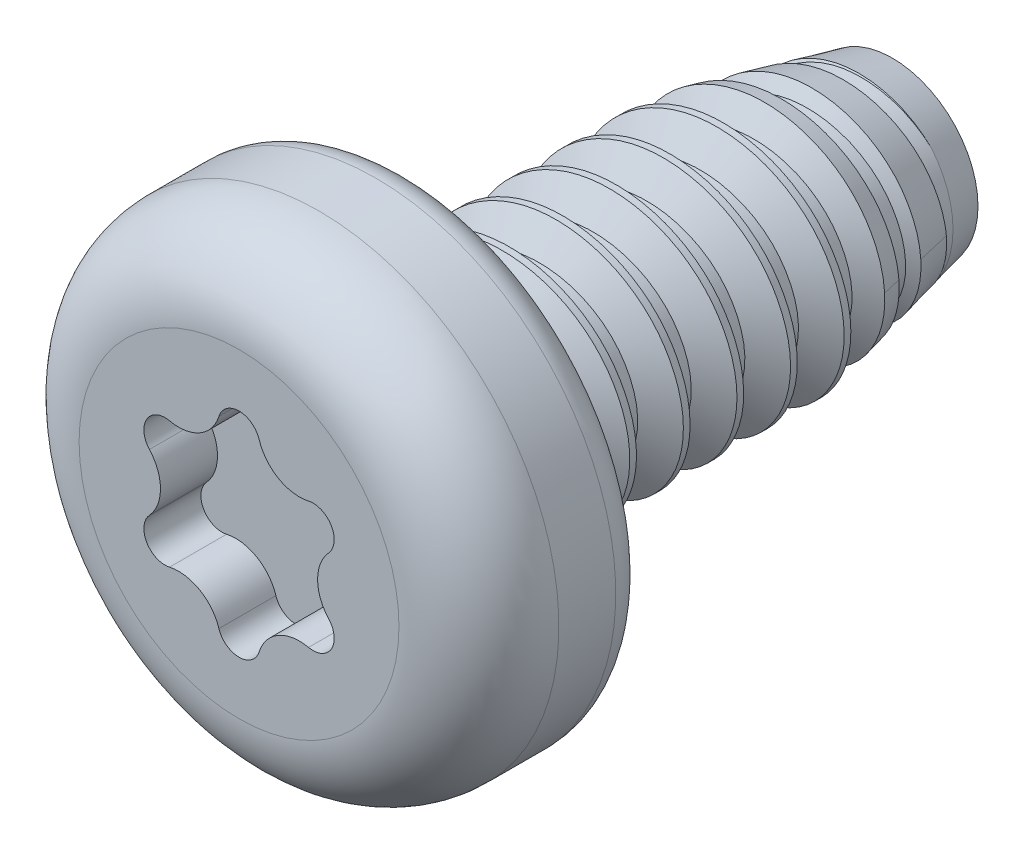
SolidWorks part; units mm, degrees
note: '?' marks a value the reader was unsure of.
ref_plane "Front" through (0, 0, 0) normal (0, 0, 1) x (1, 0, 0)
ref_plane "Top" through (0, 0, 0) normal (0, 1, 0) x (1, 0, 0)
ref_plane "Right" through (0, 0, 0) normal (1, 0, 0) x (0, 0, -1)
sketch "Sketch1" plane through (0, 0, 0) normal (0, 0, 1) x (1, 0, 0)
  circle A0 centre (0, 0) radius 4.7371
  dimension "Head Dia" = 9.4742
extrude "Extrude3" add sketch "Sketch1" along normal blind 3.3782
ref_plane "Plane1" through (0, 0, 3.3782) normal (0, 0, 1) x (1, 0, 0)
sketch "Sketch11" plane through (0, 0, 0) normal (1, 0, 0) x (0, 0, -1)
  line L2 (-3.3782, 4.7371) -> (-3.3782, -4.7371) construction
  line L4 (0, 4.7371) -> (-3.3782, 4.7371) construction
  line L5 (-1.7992, 4.7371) -> (-0.6756, 4.7371)
  line L6 (0, -4.7371) -> (0, 4.7371) construction
  line L7 (-3.3782, 4.7371) -> (-3.3782, 3.1581) construction
  line L8 (-3.3782, 1.579) -> (-3.3782, 0) construction
  line L9 (-3.3782, 3.1581) -> (-3.3782, 1.579) construction
  line L10 (-3.3782, 3.1581) -> (-3.6322, 3.1581)
  line L11 (0, 0) -> (-3.3782, 0) construction
  line L12 (-3.6322, 3.1581) -> (-3.6322, 4.9911)
  line L13 (-3.6322, 4.9911) -> (0.254, 4.9911)
  line L14 (0.254, 4.9911) -> (0.254, 4.0615)
  line L15 (0.254, 4.0615) -> (0, 4.0615)
  arc A0 (-3.3782, 3.1581) -> (-1.7992, 4.7371) centre (-1.7992, 3.1581) cw
  arc A1 (-0.6756, 4.7371) -> (0, 4.0615) centre (-0.6756, 4.0615) cw
  dimension "D1" = 0.6756
  dimension "D2" = 0.254
  dimension "D3" = 0.254
revolve "Cut-Revolve3" cut sketch "Sketch11" angle 360 about L11
sketch "Sketch14" plane through (0, 0, 0) normal (1, 0, 0) x (0, 0, -1)
  line L0 (0.2646, 1.8402) -> (0.5953, 2.413) construction
  line L2 (0.5953, 2.413) -> (0.7276, 2.413)
  line L3 (0.7276, 2.413) -> (1.0583, 1.8402) construction
  line L4 (1.0583, 1.8402) -> (0.2646, 1.8402) construction
  line L5 (1.0583, 1.8402) -> (1.3229, 1.8402) construction
  line L6 (0.2646, 1.8402) -> (0, 1.8402) construction
  line L10 (0, 4.7371) -> (0, -4.7371) construction
  line L11 (0.5953, 2.413) -> (0.2646, 1.8402)
  line L12 (0.2646, 1.8402) -> (1.0583, 1.8402)
  line L13 (1.0583, 1.8402) -> (0.7276, 2.413)
  line L14 (0, 0) -> (-3.3782, 0) construction
  line L15 (0, 0) -> (-3.3782, 0) construction
  point P11 (0.6615, 2.413)
  dimension "D1" = 60
  dimension "Pitch" = 1.0583
  dimension "D3" = 0.2646
  dimension "D4" = 0.1323
  dimension "Screw Dia" = 4.826
ref_plane "Plane2" through (0, 0, -0.6615) normal (0, 0, 1) x (1, 0, 0)
sketch "Sketch15" plane through (0, 0, -0.6615) normal (0, 0, 1) x (1, 0, 0)
  circle A0 centre (0, 0) radius 2.413
curve "Helix/Spiral1" pitch 1.0583 height 1.5875 radius 2.413 centre (0, 0, -0.6615) axis (0, 0, -1) start towards (0, 1, 0)
sketch "Sketch17" plane through (0, 0, 0) normal (1, 0, 0) x (0, 0, -1)
  line L1 (0, 0) -> (9.525, 0)
  line L2 (0, 0) -> (0, 1.8402)
  line L3 (0, 1.8402) -> (9.525, 1.8402)
  line L4 (9.525, 0) -> (9.525, 1.8402)
  dimension "Body Length" = 9.525
revolve "Revolve1" add sketch "Sketch17" angle 360 about L11
sweep "Sweep1" add profiles "Sketch14" path "Helix/Spiral1"
pattern_linear "LPattern3" count 8 spacing 1.0583 along (0, 0, -1) count 2 spacing 1.0583 along (0, 0, 1) of "Sweep1"
sketch "Sketch13" plane through (0, 0, 0) normal (1, 0, 0) x (0, 0, -1)
  line L0 (9.525, 1.6891) -> (6.4364, 2.413)
  line L1 (9.525, 1.6891) -> (9.525, -1.6891) construction
  line L2 (6.4364, 2.413) -> (9.525, 2.413)
  line L3 (9.525, 2.413) -> (9.525, 1.6891) construction
  line L4 (9.525, 1.6891) -> (9.525, 0)
  line L5 (0, 0) -> (9.525, 0) construction
  line L6 (0.5953, 2.413) -> (0.7276, 2.413) construction
  line L7 (12.065, 0) -> (12.065, 2.413)
  line L8 (12.065, 2.413) -> (9.525, 2.413)
  line L9 (9.525, 0) -> (12.065, 0)
  dimension "D3" = 2.54
  dimension "D1" = 13.191
  dimension "D2" = 3.3782
revolve "Cut-Revolve4" cut sketch "Sketch13" angle 360 about L5
sketch "Sketch12" plane through (0, 0, 3.3782) normal (0, 0, 1) x (1, 0, 0)
  line L0 (0, 0) -> (0, 2.1054) construction
  line L1 (0, 0) -> (0.7756, 1.3434) construction
  line L2 (0, 0) -> (-0.7756, 1.3434) construction
  line L3 (-0.7756, 1.3434) -> (0, 0)
  line L4 (0, 0) -> (0.7756, 1.3434)
  arc A0 (-0.7756, 1.3434) -> (-0.3975, 1.8141) centre (-1.1925, 2.0654) ccw
  arc A1 (-0.3975, 1.8141) -> (0.3975, 1.8141) centre (0, 1.6885) cw
  arc A2 (0.3975, 1.8141) -> (0.7756, 1.3434) centre (1.1925, 2.0654) ccw
  circle A5 centre (0, 0) radius 2.1054 construction
  dimension "M" = 4.2108
  dimension "D2" = 0.4169
  dimension "D3" = 0.8337
  dimension "D1" = 60
extrude "Cut-Extrude1" cut sketch "Sketch12" against normal blind 1.1261
ref_axis "Axis1" through (0, 0, 3.3782) along (0, 0, -1)?
pattern_circular "CirPattern1" count 6 every 60 about axis through (0, 0, 0) along (0, 0, 1) of "Cut-Extrude1"
combine bodies "Combine1" operation type add bodies to combine 143 123
sketch "Sketch19" plane through (0, 0, 0) normal (1, 0, 0) x (0, 0, -1)
  line L0 (5.715, 2.413) -> (5.715, -2.413) construction
  line L4 (9.525, 2.413) -> (9.525, -2.413) construction
  point P0 (-3.3782, 3.1581)
  point P1 (0, 4.0615)
  dimension "D1" = 3.81
sketch "Sketch20" plane through (0, 0, 0) normal (0, 0, 1) x (1, 0, 0)
  point P0 (1.3723, -1.2513)
equation "\"D3@LPattern3\"=\"Pitch@Sketch14\""
equation "\"D1@LPattern3\"=(\"Body Length@Sketch17\"/\"Pitch@Sketch14\")-1"
equation "\"D1@Cut-Extrude1\"=\"Head Ht@Extrude3\"/3"
equation "\"D3@Sketch14\" = \"Pitch@Sketch14\"/4"
equation "\"D4@Sketch14\" = \"Pitch@Sketch14\"/8"
equation "\"D4@LPattern3\" = \"D3@LPattern3\""
equation "\"D4@Helix/Spiral1\" = \"Pitch@Sketch14\""
equation "\"D1@Sketch11\" = \"Head Ht@Extrude3\"/5"
equation "\"M@Sketch12\" = \"Head Dia@Sketch1\"/2.25"
equation "\"D2@Sketch13\" = \"Screw Dia@Sketch14\" * .7"
equation "\"D2@Sketch12\" = \"Head Dia@Sketch1\" * .044"
equation "\"D3@Sketch12\" = \"D2@Sketch12\" * 2"
